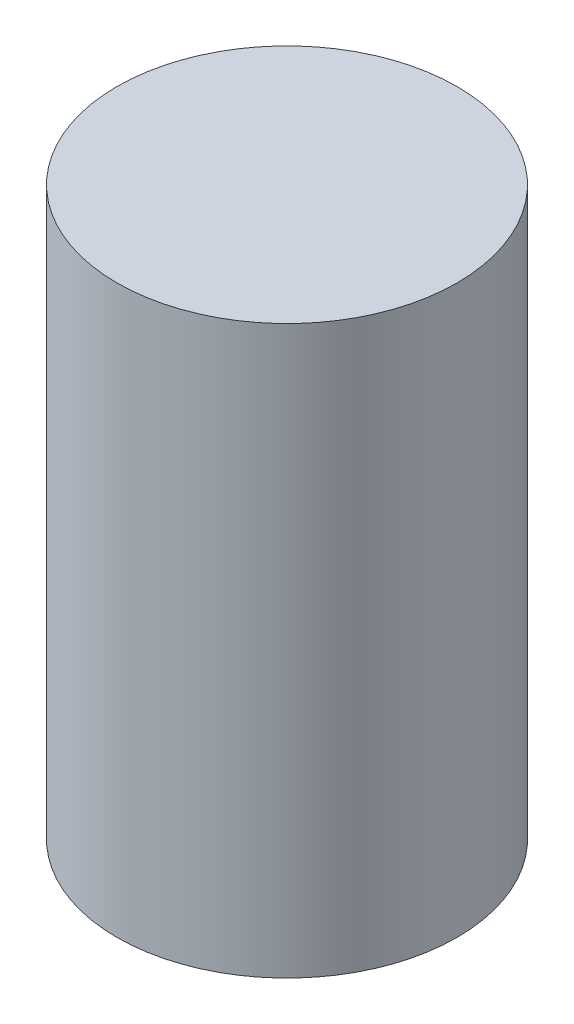
SolidWorks part; units mm, degrees
ref_plane "前视基准面" through (0, 0, 0) normal (0, 0, 1) x (1, 0, 0)
ref_plane "上视基准面" through (0, 0, 0) normal (0, 1, 0) x (1, 0, 0)
ref_plane "右视基准面" through (0, 0, 0) normal (1, 0, 0) x (0, 0, -1)
other "Configuration Table"
sketch "草图1" plane through (0, 0, 0) normal (0, 1, 0) x (1, 0, 0)
  line L5 (243.7214, -235.4106) -> (171.2273, -318.1427) construction
  line L6 (235.2846, -193.4485) -> (286.4281, -238.263)
  line L10 (235.2846, -193.4485) -> (218.1497, -213.0033)
  line L11 (218.1497, -213.0033) -> (269.2932, -257.8178)
  line L12 (286.4281, -238.263) -> (269.2932, -257.8178)
  line L13 (450, -450) -> (450, 450)
  line L14 (260.8564, -215.8557) -> (243.7214, -235.4106) construction
  line L15 (450, 0) -> (260.8564, -215.8557)
  line L16 (145.6556, -295.7355) -> (196.7991, -340.55)
  line L17 (196.7991, -340.55) -> (213.9341, -320.9951)
  line L18 (213.9341, -320.9951) -> (162.7905, -276.1806)
  line L19 (162.7905, -276.1806) -> (145.6556, -295.7355)
  line L20 (154.2231, -285.958) -> (205.3666, -330.7726) construction
  line L21 (162.7905, -276.1806) -> (269.2932, -257.8178) construction
  line L22 (216.0419, -266.9992) -> (450, -350)
  line L23 (-546.9762, 0) -> (546.9762, 0) construction
  line L38 (0, -575.0315) -> (0, 575.0315) construction
  line L41 (-450, -450) -> (450, -450)
  line L42 (-450, 450) -> (450, 450)
  line L65 (-450, -450) -> (-450, 450)
  line L66 (277.8606, -248.0404) -> (226.7171, -203.2259) construction
  circle A0 centre (0, 0) radius 300
  circle A1 centre (0, 0) radius 150
  circle A2 centre (216.0419, -266.9992) radius 328.8875
  point P17 (171.2273, -318.1427)
  point P19 (216.0419, -266.9992)
  point P20 (252.2889, -225.6331)
  point P21 (179.7948, -308.3653)
  point P22 (154.2231, -285.958)
  point P25 (226.7171, -203.2259)
  point P49 (-450, 0)
  dimension "D1" = 600
  dimension "D2" = 300
  dimension "D10" = 450
  dimension "D3" = 26
  dimension "D4" = 68
  dimension "D5" = 68
  dimension "D6" = 26
  dimension "D7" = 450
  dimension "D8" = 355
  dimension "D9" = 110
  dimension "D11" = 100
  dimension "D12" = 248.2449
extrude "凸台-拉伸1" add sketch "草图1" along normal blind 1000 contours A2 A0 A1 | A0 A2 A1 | A1 A2 | A2 A1 region at (217.9686, 0, -70.1814) region at (115.5635, 0, 142.8212) region at (-31.2886, 0, -38.6686) region at (48.5593, 0, 60.0129)
